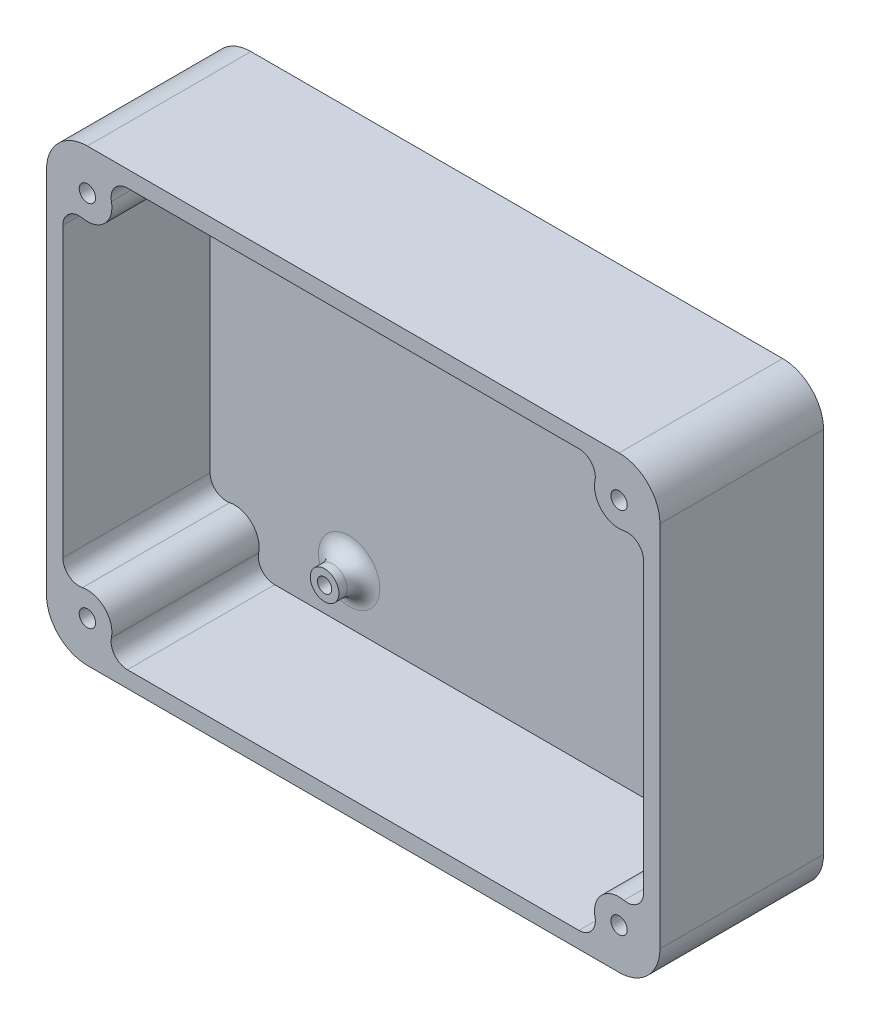
SolidWorks part; units mm, degrees
note: The reader was unsure of these and kept them because the rebuilt part matched: shared geometry of "Sketch1<3>".
ref_plane "Front Plane" through (0, 0, 0) normal (0, 0, 1) x (1, 0, 0)
ref_plane "Top Plane" through (0, 0, 0) normal (0, 1, 0) x (1, 0, 0)
ref_plane "Right Plane" through (0, 0, 0) normal (1, 0, 0) x (0, 0, -1)
sketch "Sketch1" plane through (0, 0, 0) normal (0, 0, 1) x (1, 0, 0)
  line L1 (10, 0) -> (140, 0)
  line L2 (0, 10) -> (0, 100)
  line L3 (10, 110) -> (140, 110)
  line L4 (150, 10) -> (150, 100)
  line L5 (10, 4) -> (140, 4)
  line L6 (4, 10) -> (4, 100)
  line L7 (10, 106) -> (140, 106)
  line L8 (146, 10) -> (146, 100)
  arc A0 (10, 0) -> (0, 10) centre (10, 10) cw
  arc A1 (140, 0) -> (150, 10) centre (140, 10) ccw
  arc A2 (140, 110) -> (150, 100) centre (140, 100) cw
  arc A3 (0, 100) -> (10, 110) centre (10, 100) cw
  arc A4 (10, 4) -> (4, 10) centre (10, 10) cw
  arc A5 (140, 4) -> (146, 10) centre (140, 10) ccw
  arc A6 (140, 106) -> (146, 100) centre (140, 100) cw
  arc A7 (4, 100) -> (10, 106) centre (10, 100) cw
  circle A8 centre (10, 100) radius 6
  circle A9 centre (140, 100) radius 6
  circle A10 centre (140, 10) radius 6
  circle A11 centre (10, 10) radius 6
  circle A12 centre (10, 100) radius 2
  circle A13 centre (140, 100) radius 2
  circle A14 centre (140, 10) radius 2
  circle A15 centre (10, 10) radius 2
  point P7 (0, 0)
  point P10 (150, 0)
  point P15 (0, 110)
  dimension "D3" = 10
  dimension "D8" = 6
  dimension "D9" = 4
  dimension "D1" = 110
  dimension "D2" = 150
  dimension "D4" = 4
  dimension "D5" = 4
  dimension "D6" = 4
  dimension "D7" = 4
extrude "Boss-Extrude1" add sketch "Sketch1" along normal blind 4 contours A7 L6 A4 L5 A5 L8 A6 L7
extrude "Boss-Extrude4" add sketch "Sketch1<3>" along normal blind 40 contours A7 A8 | A3 L2 A0 L1 A1 L4 A2 L3 L6 A7 L7 A6 L8 A5 L5 A4 | A6 A9 | A5 A10 | A4 A11
sketch "Sketch1<3>" plane through (0, 0, 0) normal (0, 0, 1) x (1, 0, 0) same geometry as "Sketch1"
sketch "Sketch4" plane through (0, 0, 4) normal (0, 0, 1) x (1, 0, 0)
  line L2 (150, 10) -> (150, 100) construction
  line L4 (10, 110) -> (140, 110) construction
  line L5 (35, 13) -> (128, 13) construction
  line L6 (35, 13) -> (35, 103) construction
  line L7 (35, 103) -> (128, 103) construction
  line L8 (128, 13) -> (128, 103) construction
  circle A0 centre (38, 100) radius 1.75
  circle A1 centre (38, 100) radius 3.5
  circle A2 centre (38, 16) radius 1.75
  circle A3 centre (38, 16) radius 3.5
  circle A4 centre (125, 16) radius 1.75
  circle A5 centre (125, 16) radius 3.5
  circle A6 centre (125, 100) radius 1.75
  circle A7 centre (125, 100) radius 3.5
  dimension "D1" = 3.5
  dimension "D2" = 7
  dimension "D3" = 84
  dimension "D4" = 87
  dimension "D5" = 84
  dimension "D6" = 87
  dimension "D7" = 0
  dimension "D9" = 0
  dimension "D8" = 25
  dimension "D11" = 3
  dimension "D12" = 3
  dimension "D13" = 3
  dimension "D14" = 3
  dimension "D10" = 10
fillet "Fillet3" radius 4 8 edges at (146, 10, 22) (140, 4, 22) (4, 10, 22) (10, 4, 22) (140, 106, 22) (146, 100, 22) (4, 100, 22) (10, 106, 22)
extrude "Boss-Extrude5" add sketch "Sketch4" along normal blind 6
fillet "Fillet2" radius 4 4 edges at (41.5, 16, 4) (128.5, 16, 4) (128.5, 100, 4) (41.5, 100, 4)
equation "\"D5@Sketch1\"=\"D4@Sketch1\""
equation "\"D6@Sketch1\"=\"D4@Sketch1\""
equation "\"D7@Sketch1\"=\"D4@Sketch1\""
equation "\"D5@Sketch4\"=\"D3@Sketch4\""
equation "\"D6@Sketch4\"=\"D4@Sketch4\""
